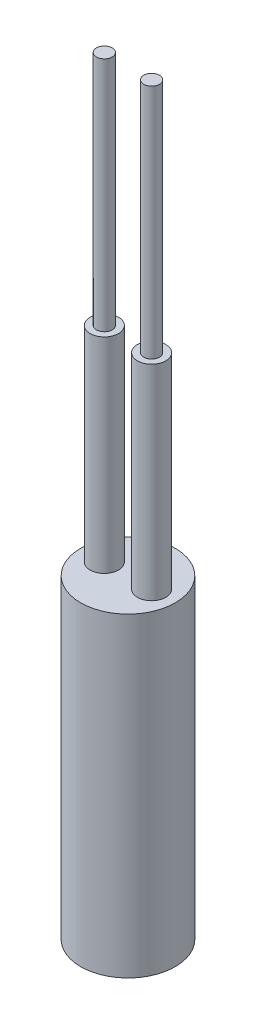
SolidWorks part; units mm, degrees
ref_plane "Front Plane" through (0, 0, 0) normal (0, 0, 1) x (1, 0, 0)
ref_plane "Top Plane" through (0, 0, 0) normal (0, 1, 0) x (1, 0, 0)
ref_plane "Right Plane" through (0, 0, 0) normal (1, 0, 0) x (0, 0, -1)
sketch "Sketch1" plane through (0, 0, 0) normal (0, 1, 0) x (1, 0, 0)
  circle A0 centre (0, 0) radius 3
  dimension "D1" = 6
extrude "Boss-Extrude1" add sketch "Sketch1" along normal blind 20
sketch "Sketch2" plane through (0, 20, 0) normal (0, 1, 0) x (1, 0, 0)
  line L0 (0, -3) -> (0, 3) construction
  circle A0 centre (1.5, 0) radius 0.9
  circle A1 centre (0, 0) radius 3 construction
  circle A2 centre (-1.5, 0) radius 0.9
  dimension "D1" = 1.8
  dimension "D2" = 3
extrude "Boss-Extrude2" add sketch "Sketch2" along normal blind 13
sketch "Sketch3" plane through (0, 33, 0) normal (0, 1, 0) x (1, 0, 0)
  circle A0 centre (1.5, 0) radius 0.5
  circle A1 centre (-1.5, 0) radius 0.5
  dimension "D1" = 1
extrude "Boss-Extrude3" add sketch "Sketch3" along normal blind 15
